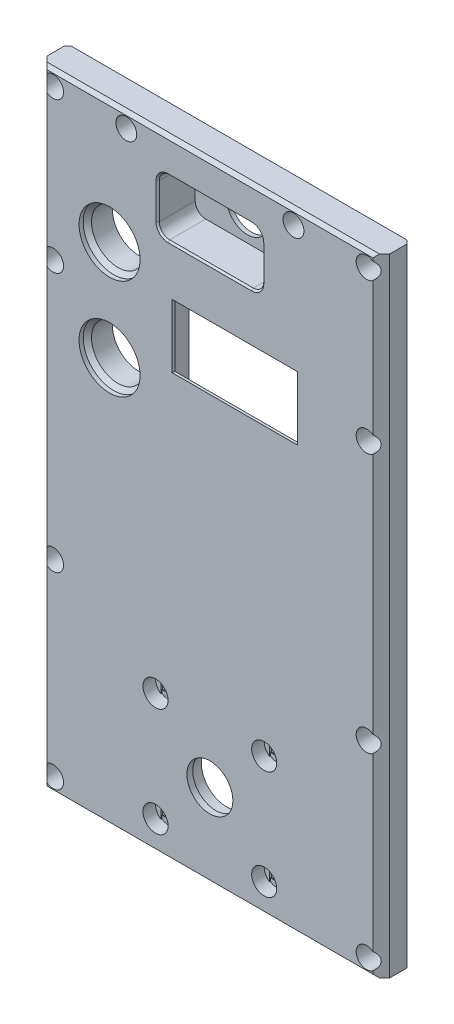
SolidWorks part; units mm, degrees
ref_plane "Front Plane" through (0, 0, 0) normal (0, 0, 1) x (1, 0, 0)
ref_plane "Top Plane" through (0, 0, 0) normal (0, 1, 0) x (1, 0, 0)
ref_plane "Right Plane" through (0, 0, 0) normal (1, 0, 0) x (0, 0, -1)
sketch "Sketch1" plane through (0, 0, 0) normal (0, 0, 1) x (1, 0, 0)
  line L1 (-41, -75) -> (41, -75)
  line L2 (-41, -75) -> (-41, 75)
  line L3 (-41, 75) -> (41, 75)
  line L4 (41, -75) -> (41, 75)
  line L5 (-41, -75) -> (41, 75) construction
  line L6 (-41, 75) -> (41, -75) construction
  line L7 (-34, -68) -> (34, -68)
  line L8 (-34, -68) -> (-34, 68)
  line L9 (-34, 68) -> (34, 68)
  line L10 (34, -68) -> (34, 68)
  line L11 (-34, -68) -> (34, 68) construction
  line L12 (-34, 68) -> (34, -68) construction
  point P0 (0, 0)
  point P6 (0, 0)
  dimension "D1" = 150
  dimension "D2" = 82
  dimension "D3" = 7
  dimension "D4" = 7
extrude "Boss-Extrude1" add sketch "Sketch1" along normal blind 7
sketch "Sketch2" plane through (0, 0, 7) normal (0, 0, 1) x (1, 0, 0)
  line L0 (34, -68) -> (34, 68) construction
  line L1 (-34, -68) -> (34, -68)
  line L2 (-34, -68) -> (-34, -32)
  line L3 (-34, -32) -> (34, -32)
  line L4 (34, -68) -> (34, -32)
  dimension "D1" = 36
extrude "Boss-Extrude2" add sketch "Sketch2" against normal up to surface (7 mm away) up to face at (0, 0, 0)
sketch "Sketch3" plane through (0, 0, 0) normal (0, 0, -1) x (-1, 0, 0)
  line L0 (0, -75) -> (0, -55) construction
  line L1 (41, -75) -> (-41, -75) construction
  circle A0 centre (0, -55) radius 5.5
  dimension "D1" = 11
  dimension "D2" = 20
extrude "Cut-Extrude1" cut sketch "Sketch3" against normal through all
sketch "Sketch4" plane through (0, 0, 0) normal (0, 0, -1) x (-1, 0, 0)
  circle A0 centre (0, -55) radius 6.05
  dimension "D1" = 12.1
extrude "Cut-Extrude2" cut sketch "Sketch4" against normal offset from surface (5.6 mm away) 1.4 up to face at (-5.5, -55, 7)
sketch "Sketch5" plane through (0, 0, 0) normal (0, 0, -1) x (-1, 0, 0)
  circle A0 centre (0, -55) radius 11.1
  dimension "D1" = 22.2
extrude "Cut-Extrude3" cut sketch "Sketch5" against normal offset from surface (3 mm away) 2.6 up to face at (-6.05, -55, 5.6)
sketch "Sketch6" plane through (0, 0, 0) normal (0, 0, -1) x (-1, 0, 0)
  line L1 (-13, -68) -> (13, -68) construction
  line L2 (-13, -68) -> (-13, -42) construction
  line L3 (-13, -42) -> (13, -42) construction
  line L4 (13, -68) -> (13, -42) construction
  line L5 (-13, -68) -> (13, -42) construction
  line L6 (-13, -42) -> (13, -68) construction
  circle A0 centre (-13, -42) radius 1.7
  circle A1 centre (13, -42) radius 1.7
  circle A2 centre (13, -68) radius 1.7
  circle A3 centre (-13, -68) radius 1.7
  point P0 (0, -55)
  dimension "D2" = 3.4
  dimension "D1" = 26
extrude "Cut-Extrude4" cut sketch "Sketch6" against normal through all
sketch "Sketch7" plane through (0, 0, 0) normal (0, 0, -1) x (-1, 0, 0)
  line L1 (-25, -74) -> (25, -74)
  line L2 (-25, -74) -> (-25, -36)
  line L3 (-25, -36) -> (25, -36)
  line L4 (25, -74) -> (25, -36)
  line L5 (-25, -74) -> (25, -36) construction
  line L6 (-25, -36) -> (25, -74) construction
  point P0 (0, -55)
  dimension "D1" = 50
  dimension "D2" = 38
extrude "Cut-Extrude5" cut sketch "Sketch7" against normal blind 1
sketch "Sketch8" plane through (0, 0, 7) normal (0, 0, 1) x (1, 0, 0)
  circle A0 centre (-13, -42) radius 3
  circle A1 centre (13, -42) radius 3
  circle A2 centre (13, -68) radius 3
  circle A3 centre (-13, -68) radius 3
  dimension "D1" = 6
extrude "Cut-Extrude6" cut sketch "Sketch8" against normal blind 3
sketch "Sketch9" plane through (0, 0, 7) normal (0, 0, 1) x (1, 0, 0)
  line L0 (-41, 75) -> (-41, -75) construction
  line L1 (-37.5, -71.5) -> (37.5, -71.5) construction
  line L2 (-37.5, -71.5) -> (-37.5, 71.5) construction
  line L3 (-37.5, 71.5) -> (37.5, 71.5) construction
  line L4 (37.5, -71.5) -> (37.5, 71.5) construction
  line L5 (-37.5, -71.5) -> (37.5, 71.5) construction
  line L6 (-37.5, 71.5) -> (37.5, -71.5) construction
  line L7 (41, 75) -> (-41, 75) construction
  circle A0 centre (-37.5, 71.5) radius 1.45
  circle A1 centre (37.5, 71.5) radius 1.45
  circle A2 centre (37.5, -71.5) radius 1.45
  circle A3 centre (-37.5, -71.5) radius 1.45
  circle A6 centre (-37.5, 35.5) radius 1.45
  circle A7 centre (-37.5, -26.5) radius 1.45
  circle A8 centre (37.5, -26.5) radius 1.45
  circle A9 centre (37.5, 35.5) radius 1.45
  point P0 (0, 0)
  dimension "D3" = 2.9
  dimension "D4" = 45
  dimension "D5" = 36
  dimension "D1" = 3.5
  dimension "D2" = 3.5
extrude "Cut-Extrude7" cut sketch "Sketch9" against normal through all
sketch "Sketch10" plane through (0, 0, 7) normal (0, 0, 1) x (1, 0, 0)
  circle A0 centre (-37.5, 71.5) radius 2.5
  circle A1 centre (37.5, 71.5) radius 2.5
  circle A2 centre (-37.5, 35.5) radius 2.5
  circle A3 centre (-37.5, -26.5) radius 2.5
  circle A4 centre (-37.5, -71.5) radius 2.5
  circle A5 centre (37.5, -71.5) radius 2.5
  circle A6 centre (37.5, 35.5) radius 2.5
  circle A7 centre (37.5, -26.5) radius 2.5
  dimension "D1" = 5
extrude "Cut-Extrude8" cut sketch "Sketch10" against normal blind 5
chamfer "Chamfer1" distance 2 angle 45 2 edges at (-41, 0, 7) (41, 0, 7)
sketch "Sketch11" plane through (0, 0, 7) normal (0, 0, 1) x (1, 0, 0)
  line L0 (34, -32) -> (34, 68) construction
  line L1 (-34, -32) -> (34, -32)
  line L2 (-34, -32) -> (-34, -1.5)
  line L3 (-34, -1.5) -> (34, -1.5)
  line L4 (34, -32) -> (34, -1.5)
  line L5 (-39, -75) -> (39, -75) construction
  dimension "D1" = 73.5
extrude "Boss-Extrude3" add sketch "Sketch11" against normal up to surface (7 mm away) up to face at (38.95, 71.5, 0)
sketch "Sketch12" plane through (0, 0, 2) normal (0, 0, 1) x (1, 0, 0)
  line L2 (-38.95, -73.5365) -> (-38.95, -69.4635)
  line L4 (-36.05, -73.5365) -> (-36.05, -69.4635)
  line L5 (-38.95, -73.5365) -> (-36.05, -69.4635) construction
  line L6 (-38.95, -69.4635) -> (-36.05, -73.5365) construction
  line L8 (-38.95, -28.5365) -> (-38.95, -24.4635)
  line L10 (-36.05, -28.5365) -> (-36.05, -24.4635)
  line L11 (-38.95, -28.5365) -> (-36.05, -24.4635) construction
  line L12 (-38.95, -24.4635) -> (-36.05, -28.5365) construction
  line L14 (-38.95, 33.4635) -> (-38.95, 37.5365)
  line L16 (-36.05, 33.4635) -> (-36.05, 37.5365)
  line L17 (-38.95, 33.4635) -> (-36.05, 37.5365) construction
  line L18 (-38.95, 37.5365) -> (-36.05, 33.4635) construction
  line L20 (-38.95, 69.4635) -> (-38.95, 73.5365)
  line L22 (-36.05, 69.4635) -> (-36.05, 73.5365)
  line L23 (-38.95, 69.4635) -> (-36.05, 73.5365) construction
  line L24 (-38.95, 73.5365) -> (-36.05, 69.4635) construction
  arc A0 (-39, -73.5) -> (-39, -69.5) centre (-37.5, -71.5) ccw construction
  circle A1 centre (-37.5, -26.5) radius 2.5 construction
  circle A2 centre (-37.5, 35.5) radius 2.5 construction
  arc A3 (-39, 69.5) -> (-39, 73.5) centre (-37.5, 71.5) ccw construction
  circle A4 centre (-37.5, 71.5) radius 1.45 construction
  circle A5 centre (-37.5, 71.5) radius 2.5 construction
  arc A6 (-36.05, 73.5365) -> (-38.95, 73.5365) centre (-37.5, 71.5) ccw
  arc A7 (-38.95, 69.4635) -> (-36.05, 69.4635) centre (-37.5, 71.5) ccw
  circle A8 centre (-37.5, 35.5) radius 1.45 construction
  arc A9 (-38.95, 33.4635) -> (-36.05, 33.4635) centre (-37.5, 35.5) ccw
  arc A10 (-36.05, 37.5365) -> (-38.95, 37.5365) centre (-37.5, 35.5) ccw
  circle A11 centre (-37.5, -26.5) radius 1.45 construction
  arc A12 (-38.95, -28.5365) -> (-36.05, -28.5365) centre (-37.5, -26.5) ccw
  arc A13 (-36.05, -24.4635) -> (-38.95, -24.4635) centre (-37.5, -26.5) ccw
  circle A14 centre (-37.5, -71.5) radius 1.45 construction
  arc A16 (-38.95, -73.5365) -> (-36.05, -73.5365) centre (-37.5, -71.5) ccw
  arc A18 (-36.05, -69.4635) -> (-38.95, -69.4635) centre (-37.5, -71.5) ccw
  point P0 (-37.5, -71.5)
  point P9 (-37.5, -26.5)
  point P17 (-37.5, 35.5)
  point P25 (-37.5, 71.5)
extrude "Cut-Extrude9" cut sketch "Sketch12" against normal blind 0.2
sketch "Sketch13" plane through (0, 0, 1.8) normal (0, 0, 1) x (1, 0, 0)
  line L0 (-36.05, -71.5) -> (-36.05, -69.4635) construction
  line L1 (-38.95, -72.95) -> (-36.05, -72.95)
  line L2 (-38.95, -72.95) -> (-38.95, -70.05)
  line L3 (-38.95, -70.05) -> (-36.05, -70.05)
  line L4 (-36.05, -72.95) -> (-36.05, -70.05)
  line L5 (-38.95, -72.95) -> (-36.05, -70.05) construction
  line L6 (-38.95, -70.05) -> (-36.05, -72.95) construction
  line L7 (-36.05, -26.5) -> (-36.05, -24.4635) construction
  line L8 (-38.95, -27.95) -> (-36.05, -27.95)
  line L9 (-38.95, -27.95) -> (-38.95, -25.05)
  line L10 (-38.95, -25.05) -> (-36.05, -25.05)
  line L11 (-36.05, -27.95) -> (-36.05, -25.05)
  line L12 (-38.95, -27.95) -> (-36.05, -25.05) construction
  line L13 (-38.95, -25.05) -> (-36.05, -27.95) construction
  line L14 (-36.05, 33.4635) -> (-36.05, 37.5365) construction
  line L15 (-38.95, 34.05) -> (-36.05, 34.05)
  line L16 (-38.95, 34.05) -> (-38.95, 36.95)
  line L17 (-38.95, 36.95) -> (-36.05, 36.95)
  line L18 (-36.05, 34.05) -> (-36.05, 36.95)
  line L19 (-38.95, 34.05) -> (-36.05, 36.95) construction
  line L20 (-38.95, 36.95) -> (-36.05, 34.05) construction
  line L21 (-36.05, 69.4635) -> (-36.05, 73.5365) construction
  line L22 (-38.95, 70.05) -> (-36.05, 70.05)
  line L23 (-38.95, 70.05) -> (-38.95, 72.95)
  line L24 (-38.95, 72.95) -> (-36.05, 72.95)
  line L25 (-36.05, 70.05) -> (-36.05, 72.95)
  line L26 (-38.95, 70.05) -> (-36.05, 72.95) construction
  line L27 (-38.95, 72.95) -> (-36.05, 70.05) construction
  arc A0 (-36.05, -71.5) -> (-38.95, -71.5) centre (-37.5, -71.5) ccw construction
  arc A1 (-36.05, -26.5) -> (-38.95, -26.5) centre (-37.5, -26.5) ccw construction
  arc A2 (-36.05, 35.5) -> (-38.95, 35.5) centre (-37.5, 35.5) ccw construction
  arc A3 (-36.05, 71.5) -> (-38.95, 71.5) centre (-37.5, 71.5) ccw construction
  point P0 (-37.5, -71.5)
  point P11 (-37.5, -26.5)
  point P22 (-37.5, 35.5)
  point P33 (-37.5, 71.5)
extrude "Cut-Extrude10" cut sketch "Sketch13" against normal blind 0.2
sketch "Sketch14" plane through (0, 0, 4) normal (0, 0, 1) x (1, 0, 0)
  line L2 (-14.7, -44.4718) -> (-14.7, -39.5282)
  line L4 (-11.3, -44.4718) -> (-11.3, -39.5282)
  line L5 (-14.7, -44.4718) -> (-11.3, -39.5282) construction
  line L6 (-14.7, -39.5282) -> (-11.3, -44.4718) construction
  line L8 (-14.7, -70.4718) -> (-14.7, -65.5282)
  line L10 (-11.3, -70.4718) -> (-11.3, -65.5282)
  line L11 (-14.7, -70.4718) -> (-11.3, -65.5282) construction
  line L12 (-14.7, -65.5282) -> (-11.3, -70.4718) construction
  circle A0 centre (-13, -42) radius 3 construction
  circle A1 centre (-13, -68) radius 3 construction
  circle A2 centre (-13, -42) radius 3 construction
  arc A3 (-14.7, -44.4718) -> (-11.3, -44.4718) centre (-13, -42) ccw
  arc A4 (-14.7, -70.4718) -> (-11.3, -70.4718) centre (-13, -68) ccw
  circle A5 centre (-13, -42) radius 1.7 construction
  circle A6 centre (-13, -68) radius 1.7 construction
  arc A7 (-11.3, -39.5282) -> (-14.7, -39.5282) centre (-13, -42) ccw
  arc A8 (-11.3, -65.5282) -> (-14.7, -65.5282) centre (-13, -68) ccw
  point P0 (-13, -42)
  point P8 (-13, -68)
extrude "Cut-Extrude11" cut sketch "Sketch14" against normal blind 0.2
sketch "Sketch15" plane through (0, 0, 3.8) normal (0, 0, 1) x (1, 0, 0)
  line L0 (-11.3, -42) -> (-11.3, -39.5282) construction
  line L1 (-14.7, -43.7) -> (-11.3, -43.7)
  line L2 (-14.7, -43.7) -> (-14.7, -40.3)
  line L3 (-14.7, -40.3) -> (-11.3, -40.3)
  line L4 (-11.3, -43.7) -> (-11.3, -40.3)
  line L5 (-14.7, -43.7) -> (-11.3, -40.3) construction
  line L6 (-14.7, -40.3) -> (-11.3, -43.7) construction
  line L7 (-11.3, -68) -> (-11.3, -65.5282) construction
  line L8 (-14.7, -69.7) -> (-11.3, -69.7)
  line L9 (-14.7, -69.7) -> (-14.7, -66.3)
  line L10 (-14.7, -66.3) -> (-11.3, -66.3)
  line L11 (-11.3, -69.7) -> (-11.3, -66.3)
  line L12 (-14.7, -69.7) -> (-11.3, -66.3) construction
  line L13 (-14.7, -66.3) -> (-11.3, -69.7) construction
  arc A0 (-11.3, -68) -> (-14.7, -68) centre (-13, -68) ccw construction
  arc A1 (-14.7, -42) -> (-11.3, -42) centre (-13, -42) ccw construction
  point P0 (-13, -42)
  point P8 (-13, -68)
extrude "Cut-Extrude12" cut sketch "Sketch15" against normal blind 0.2
mirror "Mirror1" about plane through (0, 0, 0) normal (1, 0, 0) of "Cut-Extrude10", "Cut-Extrude11", "Cut-Extrude12", "Cut-Extrude9"
chamfer "Chamfer3" distance 0.8 angle 45 4 edges at (-41, 0, 0) (41, 0, 0) (0, -75, 7) (0, 75, 7)
sketch "Sketch16" plane through (0, 0, 0) normal (1, 0, 0) x (0, 0, -1)
  line L0 (0, -4) -> (0, -15.4)
  line L1 (0, 75) -> (0, -75) construction
  line L2 (0, -15.4) -> (3.2, -12.2)
  line L3 (3.2, -12.2) -> (3.2, -7.2)
  line L4 (3.2, -7.2) -> (0, -4)
  line L5 (0, -15.4) -> (0, -19.4) construction
  line L6 (0.6, -7.7) -> (2.6, -7.7)
  line L7 (0.6, -7.7) -> (0.6, -11.7)
  line L8 (0.6, -11.7) -> (2.6, -11.7)
  line L9 (2.6, -7.7) -> (2.6, -11.7)
  line L10 (-1.046, -17.4) -> (12.8392, -17.4) construction
  line L11 (2.6, -27.1) -> (2.6, -23.1)
  line L12 (0.6, -23.1) -> (2.6, -23.1)
  line L13 (0.6, -27.1) -> (0.6, -23.1)
  line L14 (0.6, -27.1) -> (2.6, -27.1)
  line L15 (3.2, -27.6) -> (0, -30.8)
  line L16 (3.2, -22.6) -> (3.2, -27.6)
  line L17 (0, -19.4) -> (3.2, -22.6)
  line L18 (0, -30.8) -> (0, -19.4)
  point P10 (2.6, -9.7)
  point P11 (3.2, -9.7)
  point P24 (0, -17.4)
  dimension "D1" = 5
  dimension "D2" = 2
  dimension "D3" = 0.6
  dimension "D4" = 0.6
  dimension "D5" = 45
  dimension "D6" = 4
  dimension "D7" = 4
  dimension "D8" = 4
extrude "Boss-Extrude4" add sketch "Sketch16" along normal mid plane 2
pattern_linear "LPattern1" count 2 spacing 20 along (1, 0, 0) count 2 spacing 20 along (-1, 0, 0) of "Boss-Extrude4"
sketch "Sketch17" plane through (0, 0, 0) normal (0, 0, -1) x (-1, 0, 0)
  line L0 (-20, 71.5) -> (20, 71.5) construction
  line L1 (-40.2, 75) -> (40.2, 75) construction
  circle A0 centre (-37.5, 71.5) radius 1.45 construction
  circle A1 centre (-37.5, 71.5) radius 1.45 construction
  circle A2 centre (-20, 71.5) radius 1.45
  circle A3 centre (20, 71.5) radius 1.45
  point P3 (0, 71.5)
  point P6 (0, 75)
  dimension "D1" = 40
extrude "Cut-Extrude13" cut sketch "Sketch17" against normal through all
sketch "Sketch18" plane through (0, 0, 7) normal (0, 0, 1) x (1, 0, 0)
  circle A0 centre (-20, 71.5) radius 2.5
  circle A1 centre (20, 71.5) radius 2.5
  arc A2 (-39, 69.5) -> (-39, 73.5) centre (-37.5, 71.5) ccw construction
extrude "Cut-Extrude14" cut sketch "Sketch18" against normal up to surface (5 mm away) up to face at (39.475, 71.5, 2)
sketch "Sketch19" plane through (0, 0, 2) normal (0, 0, 1) x (1, 0, 0)
  line L2 (-21.45, 69.4635) -> (-21.45, 73.5365)
  line L4 (-18.55, 69.4635) -> (-18.55, 73.5365)
  line L5 (-21.45, 69.4635) -> (-18.55, 73.5365) construction
  line L6 (-21.45, 73.5365) -> (-18.55, 69.4635) construction
  line L8 (18.55, 69.4635) -> (18.55, 73.5365)
  line L10 (21.45, 69.4635) -> (21.45, 73.5365)
  line L11 (18.55, 69.4635) -> (21.45, 73.5365) construction
  line L12 (18.55, 73.5365) -> (21.45, 69.4635) construction
  circle A0 centre (-20, 71.5) radius 2.5 construction
  circle A1 centre (20, 71.5) radius 2.5 construction
  circle A2 centre (20, 71.5) radius 1.45 construction
  circle A3 centre (-20, 71.5) radius 1.45 construction
  circle A4 centre (-20, 71.5) radius 2.5 construction
  arc A5 (18.55, 69.4635) -> (21.45, 69.4635) centre (20, 71.5) ccw
  arc A6 (-18.55, 73.5365) -> (-21.45, 73.5365) centre (-20, 71.5) ccw
  arc A7 (21.45, 73.5365) -> (18.55, 73.5365) centre (20, 71.5) ccw
  arc A8 (-21.45, 69.4635) -> (-18.55, 69.4635) centre (-20, 71.5) ccw
  point P0 (-20, 71.5)
  point P8 (20, 71.5)
extrude "Cut-Extrude15" cut sketch "Sketch19" against normal blind 0.2
sketch "Sketch20" plane through (0, 0, 1.8) normal (0, 0, 1) x (1, 0, 0)
  line L0 (-18.55, 69.4635) -> (-18.55, 73.5365) construction
  line L1 (-21.45, 70.05) -> (-18.55, 70.05)
  line L2 (-21.45, 70.05) -> (-21.45, 72.95)
  line L3 (-21.45, 72.95) -> (-18.55, 72.95)
  line L4 (-18.55, 70.05) -> (-18.55, 72.95)
  line L5 (-21.45, 70.05) -> (-18.55, 72.95) construction
  line L6 (-21.45, 72.95) -> (-18.55, 70.05) construction
  line L7 (21.45, 71.5) -> (21.45, 73.5365) construction
  line L8 (18.55, 70.05) -> (21.45, 70.05)
  line L9 (18.55, 70.05) -> (18.55, 72.95)
  line L10 (18.55, 72.95) -> (21.45, 72.95)
  line L11 (21.45, 70.05) -> (21.45, 72.95)
  line L12 (18.55, 70.05) -> (21.45, 72.95) construction
  line L13 (18.55, 72.95) -> (21.45, 70.05) construction
  arc A0 (18.55, 71.5) -> (21.45, 71.5) centre (20, 71.5) ccw construction
  point P0 (-20, 71.5)
  point P8 (20, 71.5)
extrude "Cut-Extrude16" cut sketch "Sketch20" against normal blind 0.2
sketch "Skizze4" plane through (0, 0, 0) normal (0, 0, -1) x (-1, 0, 0)
  line L1 (21, -4) -> (-21, -4)
  line L2 (21, -4) -> (21, -30.8)
  line L3 (21, -30.8) -> (-21, -30.8)
  line L4 (-21, -4) -> (-21, -30.8)
extrude "Schnitt-Linear austragen1" cut sketch "Skizze4" along normal up to surface (3.2 mm away) up to face at (-20, -9.7, -3.2)
sketch "Sketch38" plane through (0, 0, 7) normal (0, 0, 1) x (1, 0, 0)
  line L0 (34, -1.5) -> (34, 68) construction
  line L1 (-34, 68) -> (34, 68)
  line L2 (-34, 68) -> (-34, 12)
  line L3 (-34, 12) -> (34, 12)
  line L4 (34, 68) -> (34, 12)
  dimension "D1" = 56
extrude "Boss-Extrude12" add sketch "Sketch38" against normal up to surface (7 mm away) up to face at (18.55, 71.5, 0)
sketch "Sketch41" plane through (0, 0, 7) normal (0, 0, 1) x (1, 0, 0)
  line L1 (-34, 12) -> (34, 12)
  line L2 (-34, 12) -> (-34, -1.5)
  line L3 (-34, -1.5) -> (34, -1.5)
  line L4 (34, 12) -> (34, -1.5)
extrude "Boss-Extrude13" add sketch "Sketch41" against normal up to surface (7 mm away) up to face at (18.55, 71.5, 0)
sketch "Sketch40" plane through (0, 0, 0) normal (0, 0, -1) x (-1, 0, 0)
  line L0 (-6, 66.6873) -> (-6, -2.4873) construction
  line L1 (-23.8, 15.25) -> (11.8, 15.25) construction
  line L2 (-23.8, 15.25) -> (-23.8, 48.95) construction
  line L3 (-23.8, 48.95) -> (11.8, 48.95) construction
  line L4 (11.8, 15.25) -> (11.8, 48.95) construction
  line L5 (-23.8, 15.25) -> (11.8, 48.95) construction
  line L6 (-23.8, 48.95) -> (11.8, 15.25) construction
  line L7 (-21.2, 17.85) -> (9.2, 17.85) construction
  line L8 (-21.2, 17.85) -> (-21.2, 46.35) construction
  line L9 (-21.2, 46.35) -> (9.2, 46.35) construction
  line L10 (9.2, 17.85) -> (9.2, 46.35) construction
  line L11 (-21.2, 17.85) -> (9.2, 46.35) construction
  line L12 (-21.2, 46.35) -> (9.2, 17.85) construction
  line L13 (-24.05, 15) -> (12.05, 15)
  line L14 (-24.05, 15) -> (-24.05, 49.2)
  line L15 (-24.05, 49.2) -> (12.05, 49.2)
  line L16 (12.05, 15) -> (12.05, 49.2)
  line L17 (-24.05, 15) -> (12.05, 49.2) construction
  line L18 (-24.05, 49.2) -> (12.05, 15) construction
  line L19 (-21, 26.4) -> (9, 26.4) construction
  line L20 (-21, 26.4) -> (-21, 41.6) construction
  line L21 (-21, 41.6) -> (9, 41.6) construction
  line L22 (9, 26.4) -> (9, 41.6) construction
  line L23 (-21, 26.4) -> (9, 41.6) construction
  line L24 (-21, 41.6) -> (9, 26.4) construction
  line L25 (-6, 34) -> (24, 34) construction
  line L26 (24, 22) -> (24, 46) construction
  circle A0 centre (-21.2, 46.35) radius 1.5 construction
  circle A1 centre (9.2, 46.35) radius 1.5 construction
  circle A2 centre (9.2, 17.85) radius 1.5 construction
  circle A3 centre (-21.2, 17.85) radius 1.5 construction
  circle A4 centre (24, 46) radius 6.3
  circle A5 centre (24, 22) radius 6.3
  circle A6 centre (24, 22) radius 7
  circle A7 centre (24, 46) radius 7
  point P2 (-6, 32.1)
  point P7 (-6, 32.1)
  point P16 (-6, 32.1)
  point P21 (-6, 34)
  point P32 (24, 34)
  dimension "D5" = 3
  dimension "D12" = 6
  dimension "D13" = 12.6
  dimension "D14" = 14
  dimension "D1" = 35.6
  dimension "D2" = 33.7
  dimension "D3" = 30.4
  dimension "D4" = 28.5
  dimension "D6" = 0.25
  dimension "D7" = 0.25
  dimension "D8" = 15.2
  dimension "D9" = 30
  dimension "D10" = 7.35
  dimension "D11" = 15
  dimension "D15" = 24
  dimension "D16" = 30
sketch "Sketch42" plane through (0, 0, 0) normal (0, 0, -1) x (-1, 0, 0)
  line L0 (-24.05, 15) -> (12.05, 15) construction
  line L1 (12.05, 15) -> (12.05, 49.2) construction
  line L2 (-24.05, 49.2) -> (12.05, 49.2) construction
  line L3 (-24.05, 15) -> (-24.05, 49.2) construction
  line L4 (-24.05, 15) -> (12.05, 15)
  line L5 (12.05, 15) -> (12.05, 49.2)
  line L6 (-24.05, 49.2) -> (12.05, 49.2)
  line L7 (-24.05, 15) -> (-24.05, 49.2)
extrude "Cut-Extrude17" cut sketch "Sketch42" against normal offset from surface (6.4 mm away) 0.6 up to face at (-17.5, 71.5, 7)
sketch "Sketch43" plane through (0, 0, 6.4) normal (0, 0, -1) x (-1, 0, 0)
  line L0 (-21, 26.4) -> (-21, 41.6) construction
  line L1 (-21, 26.4) -> (9, 26.4) construction
  line L2 (9, 26.4) -> (9, 41.6) construction
  line L3 (-21, 41.6) -> (9, 41.6) construction
  line L4 (-21, 26.4) -> (-21, 41.6)
  line L5 (-21, 26.4) -> (9, 26.4)
  line L6 (9, 26.4) -> (9, 41.6)
  line L7 (-21, 41.6) -> (9, 41.6)
extrude "Cut-Extrude18" cut sketch "Sketch43" against normal through all
sketch "Sketch44" plane through (0, 0, 0) normal (0, 0, -1) x (-1, 0, 0)
  circle A0 centre (24, 22) radius 6.3 construction
  circle A1 centre (24, 46) radius 6.3 construction
  circle A2 centre (24, 22) radius 6.3
  circle A3 centre (24, 46) radius 6.3
extrude "Cut-Extrude19" cut sketch "Sketch44" against normal through all
sketch "Sketch45" plane through (0, 0, 6.4) normal (0, 0, -1) x (-1, 0, 0)
  line L1 (-24.05, 49.2) -> (-19.2, 49.2)
  line L2 (-24.05, 49.2) -> (-24.05, 44.35)
  line L3 (-24.05, 44.35) -> (-19.2, 44.35)
  line L4 (-19.2, 49.2) -> (-19.2, 44.35)
  line L5 (12.05, 49.2) -> (7.2, 49.2)
  line L6 (12.05, 49.2) -> (12.05, 44.35)
  line L7 (12.05, 44.35) -> (7.2, 44.35)
  line L8 (7.2, 49.2) -> (7.2, 44.35)
  line L9 (12.05, 15) -> (7.2, 15)
  line L10 (12.05, 15) -> (12.05, 19.85)
  line L11 (12.05, 19.85) -> (7.2, 19.85)
  line L12 (7.2, 15) -> (7.2, 19.85)
  line L13 (-24.05, 15) -> (-19.2, 15)
  line L14 (-24.05, 15) -> (-24.05, 19.85)
  line L15 (-24.05, 19.85) -> (-19.2, 19.85)
  line L16 (-19.2, 15) -> (-19.2, 19.85)
  circle A0 centre (-21.2, 46.35) radius 1.5 construction
  dimension "D1" = 2
extrude "Boss-Extrude14" add sketch "Sketch45" along normal blind 1.8
sketch "Sketch46" plane through (0, 0, 4.6) normal (0, 0, -1) x (-1, 0, 0)
  circle A0 centre (9.2, 17.85) radius 1.55
  circle A1 centre (-21.2, 17.85) radius 1.55
  circle A2 centre (-21.2, 46.35) radius 1.55
  circle A3 centre (9.2, 46.35) radius 1.55
  dimension "D1" = 3.1
extrude "Boss-Extrude15" add sketch "Sketch46" along normal blind 2
sketch "Sketch47" plane through (0, 0, 0) normal (0, 0, -1) x (-1, 0, 0)
  line L1 (-28.79, 50.463) -> (15.71, 50.463)
  line L2 (-28.79, 50.463) -> (-28.79, 13.463)
  line L3 (-28.79, 13.463) -> (15.71, 13.463)
  line L4 (15.71, 50.463) -> (15.71, 13.463)
  dimension "D1" = 44.5
  dimension "D2" = 37
sketch "Sketch48" plane through (0, 0, 0) normal (0, 0, -1) x (-1, 0, 0)
  line L1 (-17.5, 51.3083) -> (17.5, 51.3083)
  line L2 (-17.5, 51.3083) -> (-17.5, 71.3083)
  line L3 (-17.5, 71.3083) -> (17.5, 71.3083)
  line L4 (17.5, 51.3083) -> (17.5, 71.3083)
  line L5 (-17.5, 51.3083) -> (17.5, 71.3083) construction
  line L6 (-17.5, 71.3083) -> (17.5, 51.3083) construction
  point P0 (0, 61.3083)
  dimension "D1" = 35
  dimension "D2" = 20
sketch "Sketch49" plane through (0, 0, 7) normal (0, 0, 1) x (1, 0, 0)
  line L0 (-39.8, 75) -> (39.8, 75) construction
  line L1 (-12.5, 53.25) -> (12.5, 53.25)
  line L2 (-12.5, 53.25) -> (-12.5, 66.75)
  line L3 (-12.5, 66.75) -> (12.5, 66.75)
  line L4 (12.5, 53.25) -> (12.5, 66.75)
  line L5 (-12.5, 53.25) -> (12.5, 66.75) construction
  line L6 (-12.5, 66.75) -> (12.5, 53.25) construction
  point P0 (0, 60)
  dimension "D1" = 25
  dimension "D2" = 13.5
  dimension "D3" = 15
extrude "Cut-Extrude20" cut sketch "Sketch49" against normal through all
sketch "Sketch50" plane through (0, 0, 0) normal (0, 0, -1) x (-1, 0, 0)
  line L0 (12.5, 66.75) -> (12.5, 53.25) construction
  line L1 (12.5, 53.25) -> (-12.5, 53.25) construction
  line L2 (-12.5, 53.25) -> (-12.5, 66.75) construction
  line L3 (-12.5, 66.75) -> (12.5, 66.75) construction
  line L4 (12.5, 66.75) -> (12.5, 53.25)
  line L5 (12.5, 53.25) -> (-12.5, 53.25)
  line L6 (-12.5, 53.25) -> (-12.5, 66.75)
  line L7 (-12.5, 66.75) -> (12.5, 66.75)
  line L8 (12.5, 66.75) -> (-12.5, 53.25) construction
  line L10 (-14.5, 51.25) -> (14.5, 51.25)
  line L11 (-14.5, 51.25) -> (-14.5, 68.75)
  line L12 (-14.5, 68.75) -> (14.5, 68.75)
  line L13 (14.5, 51.25) -> (14.5, 68.75)
  line L14 (-14.5, 51.25) -> (14.5, 68.75) construction
  line L15 (-14.5, 68.75) -> (14.5, 51.25) construction
  point P2 (0, 60)
  dimension "D1" = 2
  dimension "D2" = 2
extrude "Boss-Extrude16" add sketch "Sketch50" along normal offset from surface (2 mm away) 9 up to face at (0, 60, 7)
sketch "Sketch51" plane through (0, 0, -2) normal (0, 0, -1) x (-1, 0, 0)
  line L4 (-14.5, 51.25) -> (14.5, 51.25)
  line L5 (14.5, 51.25) -> (14.5, 68.75)
  line L6 (14.5, 68.75) -> (-14.5, 68.75)
  line L7 (-14.5, 68.75) -> (-14.5, 51.25)
  line L8 (-14.5, 51.25) -> (14.5, 51.25)
  line L9 (14.5, 51.25) -> (14.5, 68.75)
  line L10 (14.5, 68.75) -> (-14.5, 68.75)
  line L11 (-14.5, 68.75) -> (-14.5, 51.25)
  dimension "D1" = 0
extrude "Boss-Extrude17" add sketch "Sketch51" along normal blind 1
sketch "Sketch52" plane through (0, 0, -3) normal (0, 0, -1) x (-1, 0, 0)
  line L0 (14.5, 68.75) -> (-14.5, 51.25) construction
  circle A0 centre (0, 60) radius 5
  dimension "D1" = 10
extrude "Cut-Extrude21" cut sketch "Sketch52" against normal through all both and the other way through all
sketch "Sketch53" plane through (12.5, 0, 0) normal (-1, 0, 0) x (0, 0, 1)
  line L0 (-2, 66.75) -> (-2, 53.25) construction
  line L1 (-2, 62.5) -> (6.4, 62.5)
  line L2 (-2, 62.5) -> (-2, 57.5)
  line L3 (-2, 57.5) -> (6.4, 57.5)
  line L4 (6.4, 62.5) -> (6.4, 57.5)
  line L5 (7, 53.25) -> (7, 66.75) construction
  point P8 (6.4, 60)
  point P9 (7, 60)
  dimension "D1" = 0.6
  dimension "D2" = 5
extrude "Cut-Extrude22" cut sketch "Sketch53" against normal blind 6
sketch "Sketch54" plane through (0, 0, 7) normal (0, 0, 1) x (1, 0, 0)
  circle A0 centre (-24, 46) radius 7.3
  circle A1 centre (-24, 22) radius 7.3
  dimension "D1" = 14.6
extrude "Cut-Extrude23" cut sketch "Sketch54" against normal blind 1
chamfer "Chamfer4" distance 1 angle 45 2 edges at (-17.7, 22, 6) (-17.7, 46, 6)
fillet "Fillet1" radius 2.5 4 edges at (12.5, 53.25, 2.5) (-12.5, 53.25, 2.5) (12.5, 66.75, 2.5) (-12.5, 66.75, 2.5)
chamfer "Chamfer5" distance 0.4 angle 45 8 edges at (0, 53.25, 7) (11.7678, 53.9822, 7) (-11.7678, 53.9822, 7) (12.5, 60, 7) (-12.5, 60, 7) (11.7678, 66.0178, 7) (-11.7678, 66.0178, 7) (0, 66.75, 7)
